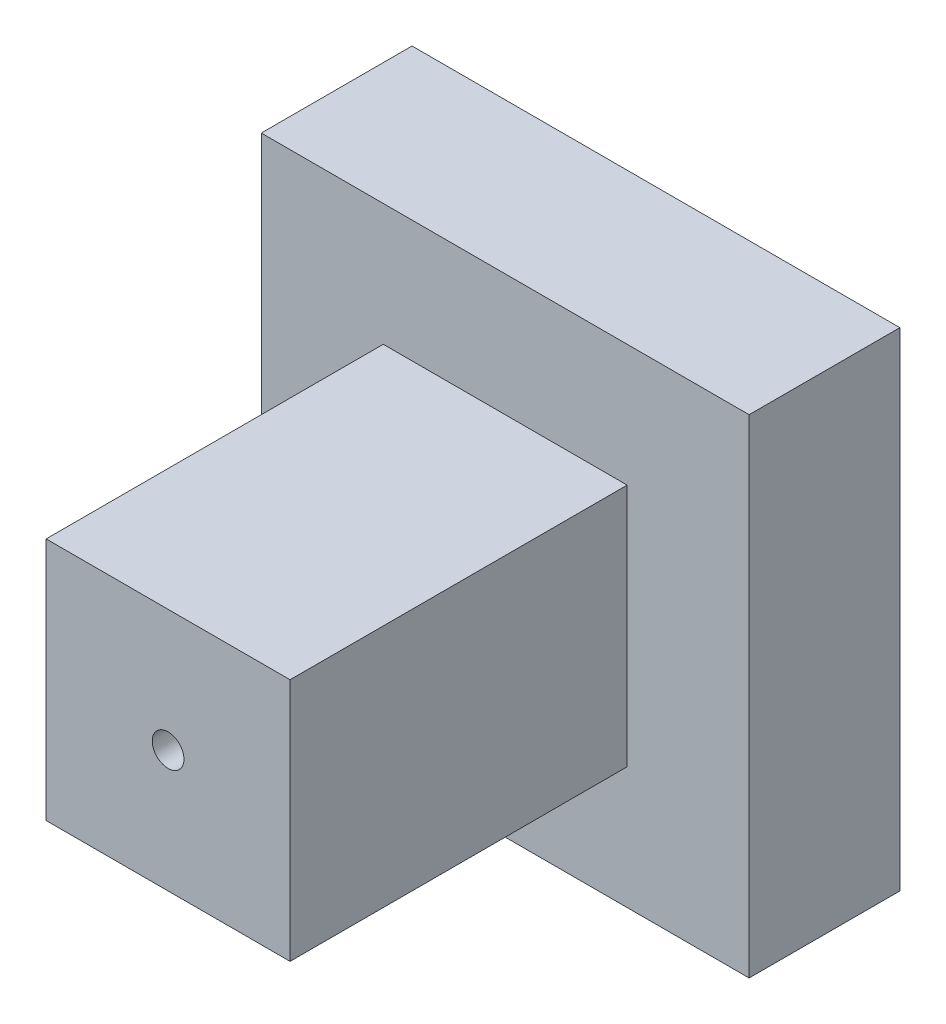
SolidWorks part; units mm, degrees
ref_plane "前视基准面" through (0, 0, 0) normal (0, 0, 1) x (1, 0, 0)
ref_plane "上视基准面" through (0, 0, 0) normal (0, 1, 0) x (1, 0, 0)
ref_plane "右视基准面" through (0, 0, 0) normal (1, 0, 0) x (0, 0, -1)
sketch "草图1" plane through (0, 0, 0) normal (0, 0, 1) x (1, 0, 0)
  line L0 (47.6235, 38.198) -> (-52.3765, -61.802)
  line L1 (-52.3765, 38.198) -> (47.6235, 38.198)
  line L2 (-52.3765, 38.198) -> (-52.3765, -61.802)
  line L3 (-52.3765, -61.802) -> (47.6235, -61.802)
  line L4 (47.6235, 38.198) -> (47.6235, -61.802)
  line L5 (47.6235, -61.802) -> (-52.3765, 38.198)
  line L9 (97.6235, 88.198) -> (-102.3765, 88.198)
  line L10 (97.6235, 88.198) -> (97.6235, -111.802)
  line L11 (97.6235, -111.802) -> (-102.3765, -111.802)
  line L12 (-102.3765, 88.198) -> (-102.3765, -111.802)
  circle A2 centre (-2.3765, -11.802) radius 6.5
  dimension "D3" = 200
  dimension "D4" = 13
  dimension "D1" = 100
  dimension "D2" = 100
extrude "凸台-拉伸2" add sketch "草图1" along normal blind 138.2 contours L4 L3 L2 L1
extrude "凸台-拉伸3" add sketch "草图1<4>" against normal blind 61.8 contours L12 L11 L10 L9
sketch "草图1<4>" plane through (0, 0, 0) normal (0, 0, 1) x (1, 0, 0) same geometry as "草图1"
extrude "切除-拉伸1" cut sketch "草图1<5>" along normal blind 177.8 contours A2
sketch "草图1<5>" plane through (0, 0, 0) normal (0, 0, 1) x (1, 0, 0) same geometry as "草图1"
